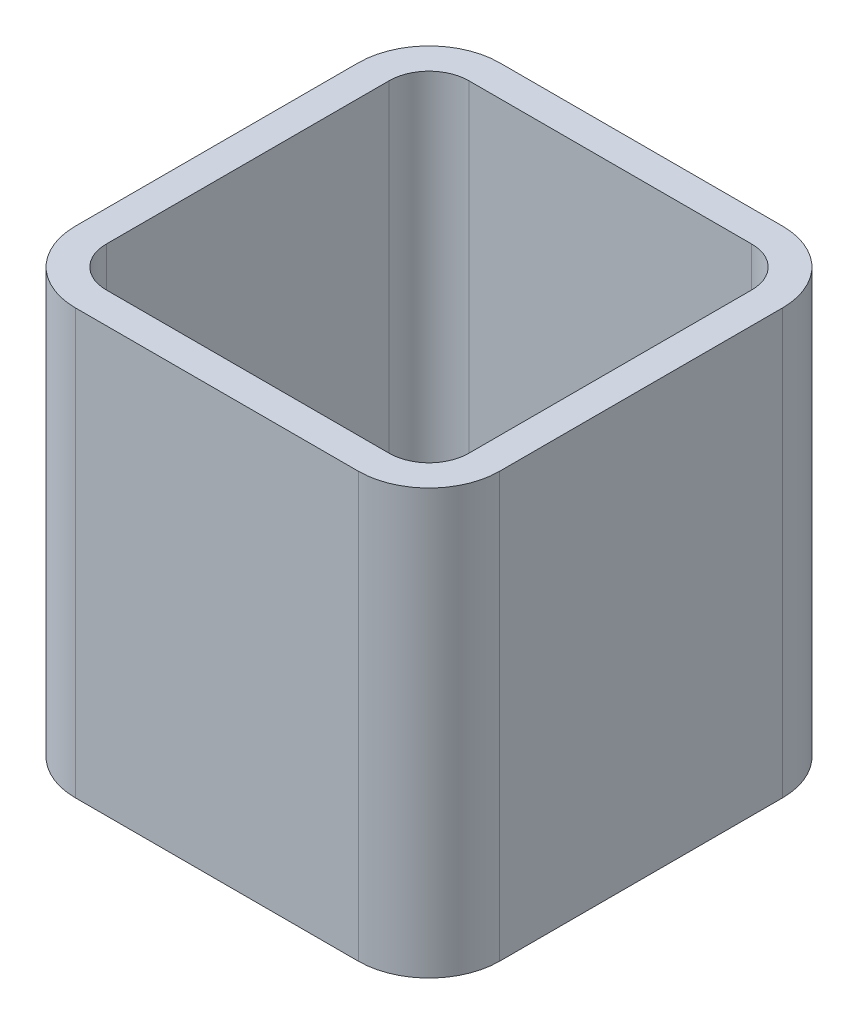
SolidWorks part; units mm, degrees
ref_plane "Front Plane" through (0, 0, 0) normal (0, 0, 1) x (1, 0, 0)
ref_plane "Top Plane" through (0, 0, 0) normal (0, 1, 0) x (1, 0, 0)
ref_plane "Right Plane" through (0, 0, 0) normal (1, 0, 0) x (0, 0, -1)
sketch "Sketch2" plane through (0, 0, 0) normal (0, 1, 0) x (1, 0, 0)
  line L1 (-101.6, 152.4) -> (101.6, 152.4)
  line L2 (-152.4, 101.6) -> (-152.4, -101.6)
  line L3 (-101.6, -152.4) -> (101.6, -152.4)
  line L4 (152.4, 101.6) -> (152.4, -101.6)
  line L5 (-152.4, 152.4) -> (152.4, -152.4) construction
  line L6 (-152.4, -152.4) -> (152.4, 152.4) construction
  arc A0 (101.6, 152.4) -> (152.4, 101.6) centre (101.6, 101.6) cw
  arc A1 (101.6, -152.4) -> (152.4, -101.6) centre (101.6, -101.6) ccw
  arc A2 (-152.4, -101.6) -> (-101.6, -152.4) centre (-101.6, -101.6) ccw
  arc A3 (-101.6, 152.4) -> (-152.4, 101.6) centre (-101.6, 101.6) ccw
  point P0 (0, 0)
  dimension "D3" = 50.8
  dimension "D1" = 304.8
  dimension "D2" = 304.8
extrude "Extrude-Thin1" add sketch "Sketch2" along normal blind 304.8 thin thin type one direction reverse wall 22.225
